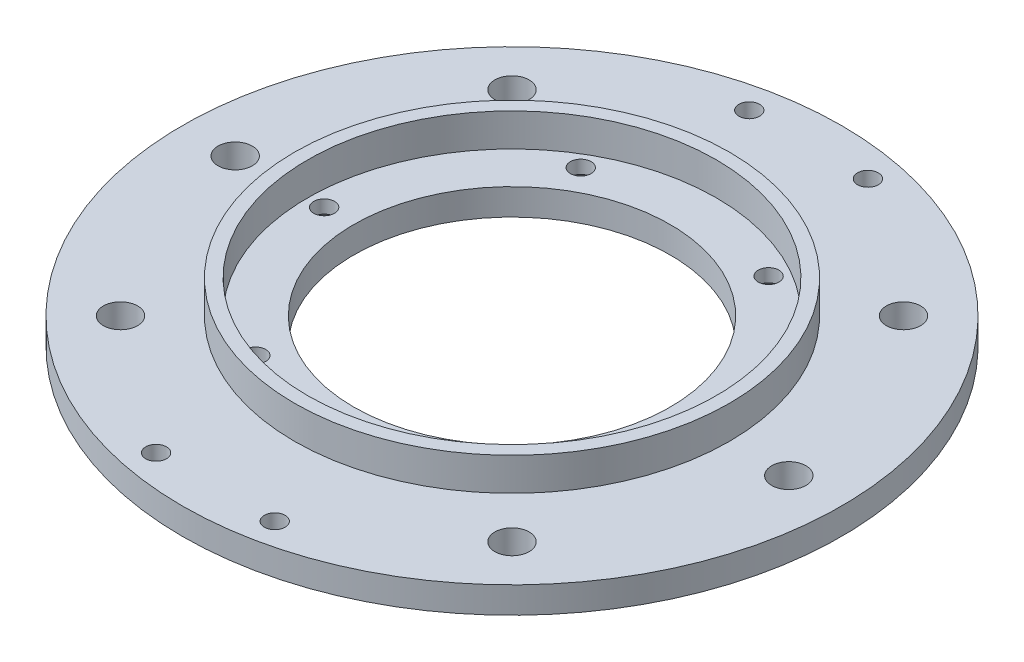
SolidWorks part; units mm, degrees
ref_plane "Спереди" through (0, 0, 0) normal (0, 0, 1) x (1, 0, 0)
ref_plane "Сверху" through (0, 0, 0) normal (0, 1, 0) x (1, 0, 0)
ref_plane "Справа" through (0, 0, 0) normal (1, 0, 0) x (0, 0, -1)
sketch "Эскиз1" plane through (0, 0, 0) normal (0, 1, 0) x (1, 0, 0)
  circle A0 centre (0, 0) radius 24
  circle A1 centre (0, 0) radius 50
  dimension "D1" = 48
  dimension "D2" = 100
extrude "Бобышка-Вытянуть1" add sketch "Эскиз1" along normal blind 4
hole_wizard "Сверло под метчик  спиральное M31" positions "Эскиз2" profile "Эскиз3" hole size "M3x0.5" standard "DIN"
sketch "Эскиз2" plane through (0, 4, 0) normal (0, 1, 0) x (1, 0, 0)
  point P0 (28.5, 0)
  dimension "D1" = 28.5
sketch "Эскиз3" plane through (28.5, 4, 0) normal (1, 0, 0) x (0, 0, 1)
  line L0 (0, 0) -> (0, 8.9464)
  line L1 (0, 8.9464) -> (1.575, 8)
  line L2 (1.575, 8) -> (1.575, 0)
  line L5 (1.575, 0) -> (0, 0)
  line L10 (0, 8.9464) -> (-1.575, 8) construction
  line L11 (0, -6.35) -> (0, 107.95) construction
  dimension "Диаметр отверстия" = 3.15
  dimension "Глубина отверстия" = 8
  dimension "Угол заточки сверла" = 118
pattern_circular "Круговой массив1" count 6 over 360 about axis through (0, 4, 0) along (0, 1, 0) of "Сверло под метчик  спиральное M31"
chamfer "Фаска1" distance 2 angle 45 6 edges at (-14.25, 0, 26.2567) (-28.5, 0, 1.575) (-14.25, 0, -23.1067) (14.25, 0, -23.1067) (28.5, 0, 1.575) (14.25, 0, 26.2567)
hole_wizard "Сверло под метчик  спиральное M32" positions "Эскиз4" profile "Эскиз5" hole size "M3x0.5" standard "DIN" end condition through all
sketch "Эскиз4" plane through (0, 0, 0) normal (0, -1, 0) x (-1, 0, 0)
  point P0 (-9, -45)
  dimension "D1" = 9
  dimension "D2" = 45
sketch "Эскиз5" plane through (9, 0, 45) normal (1, 0, 0) x (0, 0, -1)
  line L0 (0, 0) -> (0, 4)
  line L1 (0, 4) -> (1.575, 4)
  line L2 (1.575, 4) -> (1.575, 0)
  line L5 (1.575, 0) -> (0, 0)
  line L11 (0, -6.35) -> (0, 107.95) construction
  dimension "Диаметр сквозного отверстия" = 3.15
  dimension "Глубина сквозного отверстия" = 4
sketch "Эскиз6" plane through (0, 0, 0) normal (0, 1, 0) x (1, 0, 0)
  line L0 (0, 0) -> (0, 15.2777) construction
  line L1 (0, 0) -> (-12.2514, 0) construction
pattern_linear "Линейный массив1" count 2 spacing 18 along (-1, 0, 0) count 2 spacing 90 along (0, 0, -1) of "Сверло под метчик  спиральное M32"
hole_wizard "Сверло под метчик  спиральное M52" positions "Эскиз11" profile "Эскиз12" hole size "M5x0.8" standard "DIN" end condition through all
sketch "Эскиз11" plane through (0, 0, 0) normal (0, -1, 0) x (-1, 0, 0)
  point P0 (42, 0)
  point P2 (-42, 0)
  dimension "D1" = 42
  dimension "D2" = 42
sketch "Эскиз12" plane through (-42, 0, 0) normal (1, 0, 0) x (0, 0, -1)
  line L0 (0, 0) -> (0, 4)
  line L1 (0, 4) -> (2.6, 4)
  line L2 (2.6, 4) -> (2.6, 0)
  line L5 (2.6, 0) -> (0, 0)
  line L11 (0, -6.35) -> (0, 107.95) construction
  dimension "Диаметр сквозного отверстия" = 5.2
  dimension "Глубина сквозного отверстия" = 4
pattern_circular "Круговой массив3" count 2 every 45 about axis through (0, 0, 0) along (0, 1, 0) of "Сверло под метчик  спиральное M52" other way count 2
sketch "Эскиз14" plane through (0, 4, 0) normal (0, 1, 0) x (1, 0, 0)
  circle A0 centre (0, 0) radius 31
  circle A1 centre (0, 0) radius 33
  dimension "D1" = 62
  dimension "D2" = 66
extrude "Бобышка-Вытянуть2" add sketch "Эскиз14" along normal blind 5
